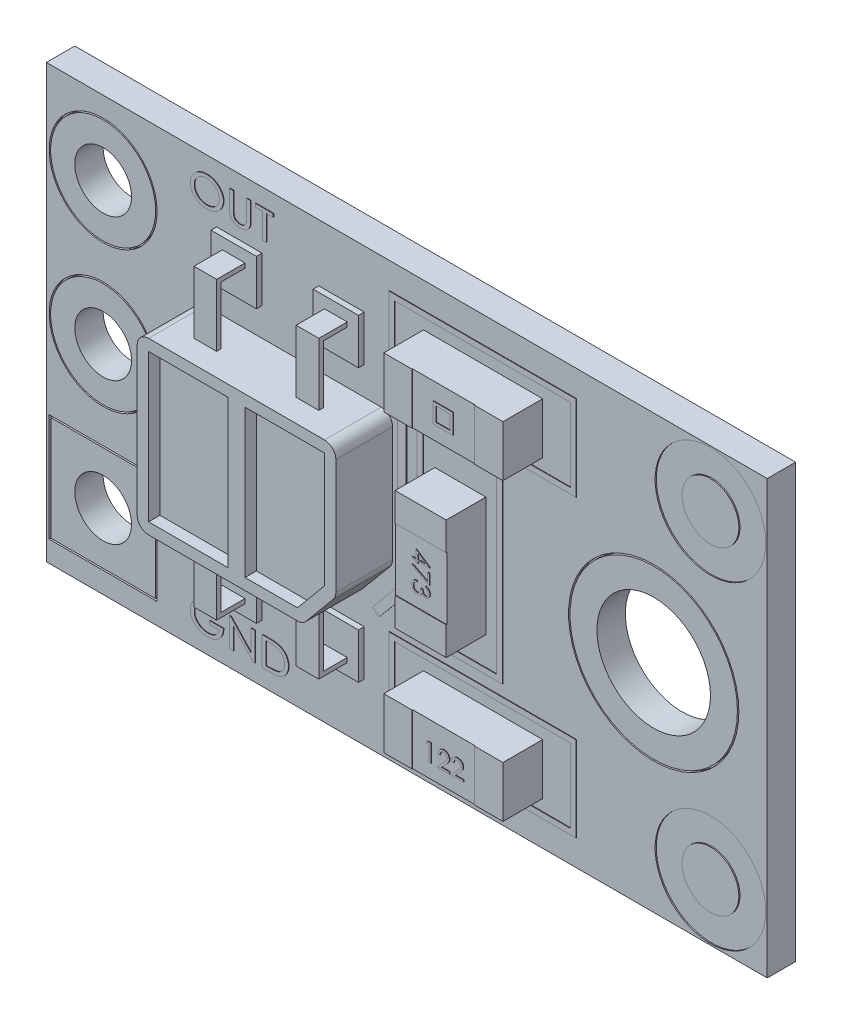
SolidWorks part; units mm, degrees
ref_plane "Alzado" through (0, 0, 0) normal (0, 0, 1) x (1, 0, 0)
ref_plane "Planta" through (0, 0, 0) normal (0, 1, 0) x (1, 0, 0)
ref_plane "Vista lateral" through (0, 0, 0) normal (1, 0, 0) x (0, 0, -1)
sketch "Croquis1" plane through (0, 0, 0) normal (0, 0, 1) x (1, 0, 0)
  line L0 (55, 0) -> (-55, 0) construction
  line L1 (-6.35, 3.81) -> (6.35, 3.81)
  line L2 (-6.35, 3.81) -> (-6.35, -3.81)
  line L3 (-6.35, -3.81) -> (6.35, -3.81)
  line L4 (6.35, 3.81) -> (6.35, -3.81)
  line L5 (0, -55) -> (0, 55) construction
  point P4 (0, 3.81)
  point P5 (-6.35, 0)
  dimension "D1" = 12.7
  dimension "D2" = 7.62
extrude "Saliente-Extruir1" add sketch "Croquis1" along normal mid plane 0.5
sketch "Croquis2" plane through (0, 0, 0.25) normal (0, 0, 1) x (1, 0, 0)
  line L1 (6.35, 3.81) -> (-6.35, 3.81) construction
  line L3 (-6.35, 3.81) -> (-6.35, -3.81) construction
  line L5 (-6.3, -1.54) -> (-4.4, -1.54)
  line L6 (-6.3, -1.54) -> (-6.3, -3.44)
  line L7 (-6.3, -3.44) -> (-4.4, -3.44)
  line L8 (-4.4, -1.54) -> (-4.4, -3.44)
  line L9 (-6.27, -1.57) -> (-4.43, -1.57)
  line L10 (-6.27, -1.57) -> (-6.27, -3.41)
  line L11 (-6.27, -3.41) -> (-4.43, -3.41)
  line L12 (-4.43, -1.57) -> (-4.43, -3.41)
  circle A2 centre (-5.35, 2.51) radius 0.95
  circle A3 centre (-5.35, 2.51) radius 0.925
  circle A4 centre (-5.35, 0.01) radius 0.95
  circle A5 centre (-5.35, 0.01) radius 0.925
  point P22 (-5.35, -1.54)
  point P23 (-6.3, -2.49)
  dimension "D9" = 1.9
  dimension "D10" = 1.85
  dimension "D11" = 1.9
  dimension "D14" = 1.85
  dimension "D7" = 1
  dimension "D8" = 1.3
  dimension "D12" = 2.5
  dimension "D13" = 1
  dimension "D15" = 1
  dimension "D16" = 0.05
  dimension "D17" = 2.5
  dimension "D18" = 0.03
  dimension "D19" = 0.03
  dimension "D20" = 0.03
extrude "Cortar-Extruir6" cut sketch "Croquis2" against normal blind 0.05
sketch "Croquis3" plane through (0, 0, 0.25) normal (0, 0, 1) x (1, 0, 0)
  circle A0 centre (-5.35, 2.51) radius 0.5
  circle A1 centre (-5.35, 0.01) radius 0.5
  circle A2 centre (-5.35, -2.49) radius 0.5
  dimension "D1" = 1
  dimension "D2" = 1
  dimension "D3" = 1
extrude "Cortar-Extruir7" cut sketch "Croquis3" against normal blind 50.05
sketch "Croquis4" plane through (0, 0, 0.25) normal (0, 0, 1) x (1, 0, 0)
  line L0 (0.275, 0) -> (-0.275, 0) construction
  line L1 (6.35, -3.81) -> (6.35, 3.81) construction
  circle A0 centre (4.35, 0) radius 1.5
  circle A1 centre (4.35, 0) radius 1.475
  dimension "D1" = 2
  dimension "D2" = 2.95
  dimension "D3" = 3
extrude "Cortar-Extruir8" cut sketch "Croquis4" against normal blind 0.05
sketch "Croquis5" plane through (0, 0, 0.25) normal (0, 0, 1) x (1, 0, 0)
  circle A0 centre (4.35, 0) radius 1
  dimension "D1" = 2
extrude "Cortar-Extruir9" cut sketch "Croquis5" against normal blind 40.05
sketch "Croquis6" plane through (0, 0, 0.25) normal (0, 0, 1) x (1, 0, 0)
  line L0 (6.35, -3.81) -> (6.35, 3.81) construction
  line L1 (6.35, 3.81) -> (-6.35, 3.81) construction
  line L2 (-6.35, -3.81) -> (6.35, -3.81) construction
  circle A0 centre (5.35, 2.81) radius 0.975
  circle A1 centre (5.35, -2.81) radius 0.975
  circle A2 centre (5.35, 2.81) radius 0.5
  circle A3 centre (5.35, -2.81) radius 0.5
  dimension "D5" = 1.95
  dimension "D6" = 1.95
  dimension "D7" = 1
  dimension "D8" = 1
  dimension "D1" = 1
  dimension "D2" = 1
  dimension "D3" = 1
  dimension "D4" = 1
extrude "Cortar-Extruir10" cut sketch "Croquis6" against normal blind 0.02
sketch "Croquis7" plane through (0, 0, 0.25) normal (0, 0, 1) x (1, 0, 0)
  line L1 (-6.35, 3.81) -> (-6.35, -3.81) construction
  line L2 (6.35, 3.81) -> (-6.35, 3.81) construction
  line L3 (-6.35, -3.81) -> (6.35, -3.81) construction
  text T0 "OUT" font "Century Gothic" height 0.5
  text T1 "GND" font "Century Gothic" height 0.5
  dimension "D1" = 2.5
  dimension "D2" = 0.8
  dimension "D3" = 0.3
  dimension "D4" = 2.5
extrude "Saliente-Extruir2" add sketch "Croquis7" along normal blind 0.01
sketch "Croquis8" plane through (0, 0, 0.25) normal (0, 0, 1) x (1, 0, 0)
  line L0 (0.2805, 0) -> (-0.2805, 0) construction
  line L1 (0.1938, 1.65) -> (1.6938, 1.65)
  line L2 (0.1938, 1.65) -> (0.1938, -1.65)
  line L3 (0.1938, -1.65) -> (1.6938, -1.65)
  line L4 (1.6938, 1.65) -> (1.6938, -1.65)
  line L6 (0.2938, 1.55) -> (1.5938, 1.55)
  line L7 (0.2938, 1.55) -> (0.2938, -1.55)
  line L8 (0.2938, -1.55) -> (1.5938, -1.55)
  line L9 (1.5938, 1.55) -> (1.5938, -1.55)
  line L10 (-0.3062, 3.35) -> (2.9938, 3.35)
  line L11 (-0.3062, 3.35) -> (-0.3062, 1.85)
  line L12 (-0.3062, 1.85) -> (2.9938, 1.85)
  line L13 (2.9938, 3.35) -> (2.9938, 1.85)
  line L14 (-0.2062, 3.25) -> (2.8938, 3.25)
  line L15 (-0.2062, 3.25) -> (-0.2062, 1.95)
  line L16 (-0.2062, 1.95) -> (2.8938, 1.95)
  line L17 (2.8938, 3.25) -> (2.8938, 1.95)
  line L18 (-0.3062, -1.85) -> (2.9938, -1.85)
  line L19 (-0.3062, -1.85) -> (-0.3062, -3.35)
  line L20 (-0.3062, -3.35) -> (2.9938, -3.35)
  line L21 (2.9938, -1.85) -> (2.9938, -3.35)
  line L22 (-0.2062, -1.95) -> (2.8938, -1.95)
  line L23 (-0.2062, -1.95) -> (-0.2062, -3.25)
  line L24 (-0.2062, -3.25) -> (2.8938, -3.25)
  line L25 (2.8938, -1.95) -> (2.8938, -3.25)
  point P4 (1.6938, 0)
  dimension "D1" = 1.5
  dimension "D2" = 3.3
  dimension "D3" = 0.1
  dimension "D4" = 0.1
  dimension "D5" = 0.1
  dimension "D6" = 0.1
  dimension "D7" = 3.3
  dimension "D8" = 0.2
  dimension "D9" = 0.5
  dimension "D10" = 0.1
  dimension "D11" = 0.1
  dimension "D12" = 0.1
  dimension "D13" = 0.1
  dimension "D14" = 1.5
  dimension "D15" = 0.2
  dimension "D16" = 1.5
  dimension "D17" = 3.3
  dimension "D18" = 0.1
  dimension "D19" = 0.1
  dimension "D20" = 0.1
  dimension "D21" = 0.1
extrude "Saliente-Extruir3" add sketch "Croquis8" along normal blind 0.01
sketch "Croquis9" plane through (0, 0, 0.25) normal (0, 0, 1) x (1, 0, 0)
  line L0 (-4.3, 0.935) -> (-4.3, -0.902) construction
  line L1 (-6.35, 3.81) -> (-6.35, -3.81) construction
  text T0 "VIN" font "Century Gothic" height 0.5
  dimension "D1" = 2.05
extrude "Saliente-Extruir4" add sketch "Croquis9" along normal blind 0.01
sketch "Croquis11" plane through (0, 0, 0.25) normal (0, 0, 1) x (1, 0, 0)
  line L0 (-3.75, -1.3) -> (-3.75, 1.3)
  line L1 (-3.55, -1.5) -> (-0.9271, -1.5)
  line L2 (-0.7734, -1.428) -> (-0.2964, -0.8556)
  line L3 (-0.25, -0.7276) -> (-0.25, 1.3)
  line L5 (-0.45, 1.5) -> (-3.55, 1.5)
  line L6 (-6.35, 3.81) -> (-6.35, -3.81) construction
  line L7 (0.2805, 0) -> (-0.2805, 0) construction
  arc A0 (-0.25, -0.7276) -> (-0.2964, -0.8556) centre (-0.45, -0.7276) cw
  arc A1 (-0.9271, -1.5) -> (-0.7734, -1.428) centre (-0.9271, -1.3) ccw
  arc A2 (-0.25, 1.3) -> (-0.45, 1.5) centre (-0.45, 1.3) ccw
  arc A3 (-3.55, -1.5) -> (-3.75, -1.3) centre (-3.55, -1.3) cw
  arc A4 (-3.55, 1.5) -> (-3.75, 1.3) centre (-3.55, 1.3) ccw
  point P7 (-3.75, 0)
  point P12 (-0.25, -0.8)
  point P17 (-0.25, 1.5)
  point P20 (-3.75, -1.5)
  point P23 (-3.75, 1.5)
  dimension "D5" = 0.2
  dimension "D1" = 3
  dimension "D2" = 3.5
  dimension "D3" = 2.6
  dimension "D4" = 2.3
extrude "Saliente-Extruir5" add sketch "Croquis11" along normal blind 1
sketch "Croquis12" plane through (0, 0, 1.25) normal (0, 0, 1) x (1, 0, 0)
  line L0 (-3.55, -1.3) -> (-3.55, 1.3)
  line L1 (-3.55, 1.3) -> (-2.15, 1.3)
  line L2 (-0.45, 1.3) -> (-0.45, -0.7276)
  line L3 (-0.45, -0.7276) -> (-0.9271, -1.3)
  line L4 (-0.9271, -1.3) -> (-1.85, -1.3)
  line L5 (-2.15, 1.3) -> (-2.15, -1.3)
  line L7 (-1.85, -1.3) -> (-1.85, 1.3)
  line L8 (-1.85, 1.3) -> (-0.45, 1.3)
  line L9 (-2.15, -1.3) -> (-3.55, -1.3)
  dimension "D1" = 1.4
  dimension "D2" = 1.4
extrude "Cortar-Extruir11" cut sketch "Croquis12" against normal blind 0.2
sketch "Croquis13" plane through (0, 0, 0.25) normal (0, 0, 1) x (1, 0, 0)
  line L0 (-3.35, 2) -> (-2.55, 2)
  line L2 (-0.45, 1.5) -> (-3.55, 1.5) construction
  line L3 (-3.55, -1.5) -> (-0.9271, -1.5) construction
  line L4 (-1.55, 2.8) -> (-0.75, 2.8)
  line L5 (-1.55, 2.8) -> (-1.55, 2)
  line L6 (-3.35, 2) -> (-3.35, 2.8)
  line L7 (-3.35, 2.8) -> (-2.55, 2.8)
  line L8 (-2.55, 2.8) -> (-2.55, 2)
  line L9 (-1.55, 2) -> (-0.75, 2)
  line L10 (-3.75, 1.3) -> (-3.75, -1.3) construction
  line L11 (-0.75, 2.8) -> (-0.75, 2)
  line L12 (-3.35, -2) -> (-2.55, -2)
  line L13 (-3.35, -2) -> (-3.35, -2.8)
  line L14 (-3.35, -2.8) -> (-2.55, -2.8)
  line L15 (-2.55, -2) -> (-2.55, -2.8)
  line L16 (-1.55, -2) -> (-0.75, -2)
  line L17 (-1.55, -2) -> (-1.55, -2.8)
  line L18 (-1.55, -2.8) -> (-0.75, -2.8)
  line L19 (-0.75, -2) -> (-0.75, -2.8)
  dimension "D1" = 0.8
  dimension "D2" = 0.8
  dimension "D3" = 0.5
  dimension "D4" = 0.4
  dimension "D5" = 0.8
  dimension "D6" = 0.8
  dimension "D7" = 1
  dimension "D8" = 0.5
  dimension "D9" = 0.5
  dimension "D10" = 1
  dimension "D11" = 0.8
  dimension "D12" = 0.8
  dimension "D13" = 0.8
  dimension "D14" = 0.8
  dimension "D15" = 0.4
extrude "Saliente-Extruir6" add sketch "Croquis13" along normal blind 0.1
sketch "Croquis14" plane through (0, 0, 0.35) normal (0, 0, 1) x (1, 0, 0)
  line L0 (-3.15, -2.6) -> (-3.15, -1.5)
  line L1 (-3.55, -1.5) -> (-0.9271, -1.5) construction
  line L2 (-3.15, -1.5) -> (-2.75, -1.5)
  line L3 (-2.75, -1.5) -> (-2.75, -2.6)
  line L4 (-2.75, -2.6) -> (-3.15, -2.6)
  line L5 (-3.35, -2) -> (-3.35, -2.8) construction
  line L6 (-2.55, -2.8) -> (-2.55, -2) construction
  line L7 (-3.35, -2.8) -> (-2.55, -2.8) construction
  line L8 (-1.35, -2.6) -> (-1.35, -1.5)
  line L9 (-3.55, -1.5) -> (-0.9271, -1.5) construction
  line L10 (-1.35, -1.5) -> (-0.95, -1.5)
  line L11 (-0.95, -1.5) -> (-0.95, -2.6)
  line L12 (-0.95, -2.6) -> (-1.35, -2.6)
  line L13 (-1.55, -2) -> (-1.55, -2.8) construction
  line L14 (-0.75, -2.8) -> (-0.75, -2) construction
  line L15 (-3.15, 1.5) -> (-3.15, 2.6)
  line L16 (-0.45, 1.5) -> (-3.55, 1.5) construction
  line L17 (-3.15, 2.6) -> (-2.75, 2.6)
  line L18 (-2.75, 2.6) -> (-2.75, 1.5)
  line L19 (-2.75, 1.5) -> (-3.15, 1.5)
  line L21 (-2.55, 2.8) -> (-3.35, 2.8) construction
  line L22 (-1.35, 2.6) -> (-0.95, 2.6)
  line L23 (-0.95, 2.6) -> (-0.95, 1.5)
  line L24 (-0.45, 1.5) -> (-3.55, 1.5) construction
  line L25 (-0.95, 1.5) -> (-1.35, 1.5)
  line L26 (-1.35, 1.5) -> (-1.35, 2.6)
  point P20 (-0.75, -2.4)
  dimension "D1" = 0.2
  dimension "D2" = 0.2
  dimension "D3" = 0.2
  dimension "D4" = 0.2
  dimension "D5" = 0.2
  dimension "D6" = 0.2
extrude "Saliente-Extruir7" add sketch "Croquis14" along normal blind 0.5
sketch "Croquis15" plane through (-0.95, 0, 0) normal (1, 0, 0) x (0, 0, -1)
  line L0 (-0.35, -2.52) -> (-0.77, -2.52)
  line L1 (-0.35, -2.6) -> (-0.35, -2) construction
  line L2 (-0.77, -2.52) -> (-0.77, -1.5)
  line L3 (-0.85, -1.5) -> (-0.35, -1.5) construction
  line L4 (-0.77, -1.5) -> (-0.35, -1.5)
  line L5 (-0.35, -1.5) -> (-0.35, -2.52)
  line L6 (-0.85, -2.6) -> (-0.85, -1.5) construction
  line L7 (-0.85, -2.6) -> (-0.35, -2.6) construction
  dimension "D1" = 0.08
  dimension "D2" = 0.08
extrude "Cortar-Extruir12" cut sketch "Croquis15" against normal blind 20.5
sketch "Croquis16" plane through (-0.95, 0, 0) normal (1, 0, 0) x (0, 0, -1)
  line L0 (-0.77, 1.5) -> (-0.77, 2.52)
  line L1 (-0.85, 1.5) -> (-0.35, 1.5) construction
  line L2 (-0.77, 2.52) -> (-0.35, 2.52)
  line L3 (-0.35, 2) -> (-0.35, 2.6) construction
  line L4 (-0.35, 2.52) -> (-0.35, 1.5)
  line L5 (-0.35, 1.5) -> (-0.77, 1.5)
  line L6 (-0.77, 1.5) -> (-0.7672, 1.4972)
  line L7 (-0.85, 1.5) -> (-0.85, 2.6) construction
  line L9 (-0.85, 2.6) -> (-0.35, 2.6) construction
  line M3 (-0.35, 1.5) -> (-0.35, 2)
  line M4 (-0.35, 2) -> (-0.35, 2.6)
  line M7 (-0.85, 1.5) -> (-0.35, 1.5)
  dimension "D1" = 0.08
  dimension "D2" = 0.08
extrude "Cortar-Extruir13" cut sketch "Croquis16" against normal blind 11 contours L2 L0 M7 M3 M4 region at (-0.95, 2.01, 0.56)
sketch "Croquis17" plane through (0, 0, 0.25) normal (0, 0, 1) x (1, 0, 0)
  line L0 (-0.5936, -1.6159) -> (-0.15, -1.0837)
  line L1 (-0.15, -1.0837) -> (-0.15, 1.65)
  line L2 (-0.15, 1.65) -> (0, 1.65)
  line L3 (0, -0.825) -> (0, 0.825) construction
  line L4 (0, 1.65) -> (0, -1.138)
  line L5 (0, -1.138) -> (-0.4784, -1.7119)
  line L6 (-0.4784, -1.7119) -> (-0.5936, -1.6159)
  line L7 (1.6938, 1.65) -> (0.1938, 1.65) construction
  dimension "D1" = 0.15
  dimension "D2" = 0.15
  dimension "D3" = 0
extrude "Saliente-Extruir8" add sketch "Croquis17" along normal blind 0.01
sketch "Croquis18" plane through (0, 0, 0.25) normal (0, 0, 1) x (1, 0, 0)
  line L1 (2.8938, 3.25) -> (-0.2062, 3.25) construction
  line L2 (0.2938, 3.05) -> (2.3938, 3.05)
  line L3 (0.2938, 3.05) -> (0.2938, 2.15)
  line L4 (0.2938, 2.15) -> (2.3938, 2.15)
  line L7 (2.8938, 1.95) -> (2.8938, 3.25) construction
  line L8 (-0.2062, 3.25) -> (-0.2062, 1.95) construction
  line L10 (2.3938, 3.05) -> (2.3938, 2.15)
  line L11 (-0.2062, 1.95) -> (2.8938, 1.95) construction
  line L12 (-0.2062, -3.25) -> (2.8938, -3.25) construction
  line L13 (0.4938, 1.05) -> (1.3938, 1.05)
  line L14 (0.4938, 1.05) -> (0.4938, -1.05)
  line L15 (0.4938, -1.05) -> (1.3938, -1.05)
  line L16 (1.3938, 1.05) -> (1.3938, -1.05)
  line L17 (0.2938, -2.15) -> (2.3938, -2.15)
  line L18 (0.2938, -2.15) -> (0.2938, -3.05)
  line L19 (0.2938, -3.05) -> (2.3938, -3.05)
  line L20 (2.3938, -2.15) -> (2.3938, -3.05)
  line L21 (2.8938, -1.95) -> (-0.2062, -1.95) construction
  line L22 (2.8938, -3.25) -> (2.8938, -1.95) construction
  line L23 (-0.2062, -1.95) -> (-0.2062, -3.25) construction
  line L24 (0.2938, -1.55) -> (1.5938, -1.55) construction
  line L25 (1.5938, 1.55) -> (0.2938, 1.55) construction
  line L26 (1.5938, -1.55) -> (1.5938, 1.55) construction
  line L27 (0.2938, 1.55) -> (0.2938, -1.55) construction
  dimension "D1" = 0.5
  dimension "D2" = 0.5
  dimension "D3" = 0.2
  dimension "D4" = 0.2
  dimension "D5" = 0.2
  dimension "D6" = 0.2
  dimension "D7" = 0.5
  dimension "D8" = 0.5
  dimension "D9" = 0.5
  dimension "D10" = 0.5
  dimension "D11" = 0.2
  dimension "D12" = 0.2
extrude "Saliente-Extruir9" add sketch "Croquis18" along normal blind 0.7
sketch "Croquis19" plane through (0, 0, 0.95) normal (0, 0, 1) x (1, 0, 0)
  line L0 (0.2938, 2.15) -> (2.3938, 2.15) construction
  line L1 (0.7938, 2.15) -> (1.8938, 2.15)
  line L2 (0.7938, 2.15) -> (0.7938, 3.05)
  line L3 (0.7938, 3.05) -> (1.8938, 3.05)
  line L4 (1.8938, 2.15) -> (1.8938, 3.05)
  line L5 (2.3938, 3.05) -> (0.2938, 3.05) construction
  line L6 (0.2938, 3.05) -> (0.2938, 2.15) construction
  line L7 (2.3938, 2.15) -> (2.3938, 3.05) construction
  line L8 (0.4938, 1.05) -> (0.4938, -1.05) construction
  line L9 (0.4938, 0.55) -> (1.3938, 0.55)
  line L10 (0.4938, 0.55) -> (0.4938, -0.55)
  line L11 (0.4938, -0.55) -> (1.3938, -0.55)
  line L12 (1.3938, 0.55) -> (1.3938, -0.55)
  line L13 (1.3938, -1.05) -> (1.3938, 1.05) construction
  line L14 (1.3938, 1.05) -> (0.4938, 1.05) construction
  line L15 (0.4938, -1.05) -> (1.3938, -1.05) construction
  line L16 (2.3938, -2.15) -> (0.2938, -2.15) construction
  line L17 (0.7938, -2.15) -> (1.8938, -2.15)
  line L18 (0.7938, -2.15) -> (0.7938, -3.05)
  line L19 (0.7938, -3.05) -> (1.8938, -3.05)
  line L20 (1.8938, -2.15) -> (1.8938, -3.05)
  line L21 (0.2938, -3.05) -> (2.3938, -3.05) construction
  line L22 (2.3938, -3.05) -> (2.3938, -2.15) construction
  line L23 (0.2938, -2.15) -> (0.2938, -3.05) construction
  dimension "D1" = 0.5
  dimension "D2" = 0.5
  dimension "D3" = 0.5
  dimension "D4" = 0.5
  dimension "D5" = 0.5
  dimension "D6" = 0.5
extrude "Cortar-Extruir14" cut sketch "Croquis19" against normal blind 0.01
sketch "Croquis20" plane through (0, 0, 0.94) normal (0, 0, 1) x (1, 0, 0)
  line L0 (0.7938, 0.55) -> (0.7938, -0.55) construction
  line L1 (1.3938, 0.55) -> (0.4938, 0.55) construction
  line L2 (0.4938, -0.55) -> (1.3938, -0.55) construction
  line L3 (0.4938, 1.05) -> (0.4938, -1.05) construction
  line L5 (1.2138, 2.7) -> (1.4638, 2.7)
  line L6 (1.2138, 2.7) -> (1.2138, 2.45)
  line L7 (1.2138, 2.45) -> (1.4638, 2.45)
  line L8 (1.4638, 2.7) -> (1.4638, 2.45)
  line L9 (1.1638, 2.75) -> (1.5138, 2.75)
  line L10 (1.1638, 2.75) -> (1.1638, 2.4)
  line L11 (1.1638, 2.4) -> (1.5138, 2.4)
  line L12 (1.5138, 2.75) -> (1.5138, 2.4)
  line L14 (1.8938, 2.15) -> (1.8938, 3.05) construction
  line L16 (0.2938, 2.15) -> (2.3938, 2.15) construction
  line L17 (0.7938, -2.8) -> (1.8938, -2.8) construction
  line L18 (0.7938, -2.15) -> (0.7938, -3.05) construction
  line L19 (1.8938, -3.05) -> (1.8938, -2.15) construction
  line L20 (0.7938, -3.05) -> (1.8938, -3.05) construction
  text T0 "473" font "Century Gothic" height 0.305
  text T1 "122\r\n\r\n" font "Century Gothic" height 0.31
  dimension "D1" = 0.3
  dimension "D2" = 0.05
  dimension "D3" = 0.05
  dimension "D4" = 0.05
  dimension "D5" = 0.05
  dimension "D6" = 0.35
  dimension "D7" = 0.38
  dimension "D8" = 0.25
  dimension "D9" = 0.25
extrude "Saliente-Extruir10" add sketch "Croquis20" along normal blind 0.01
